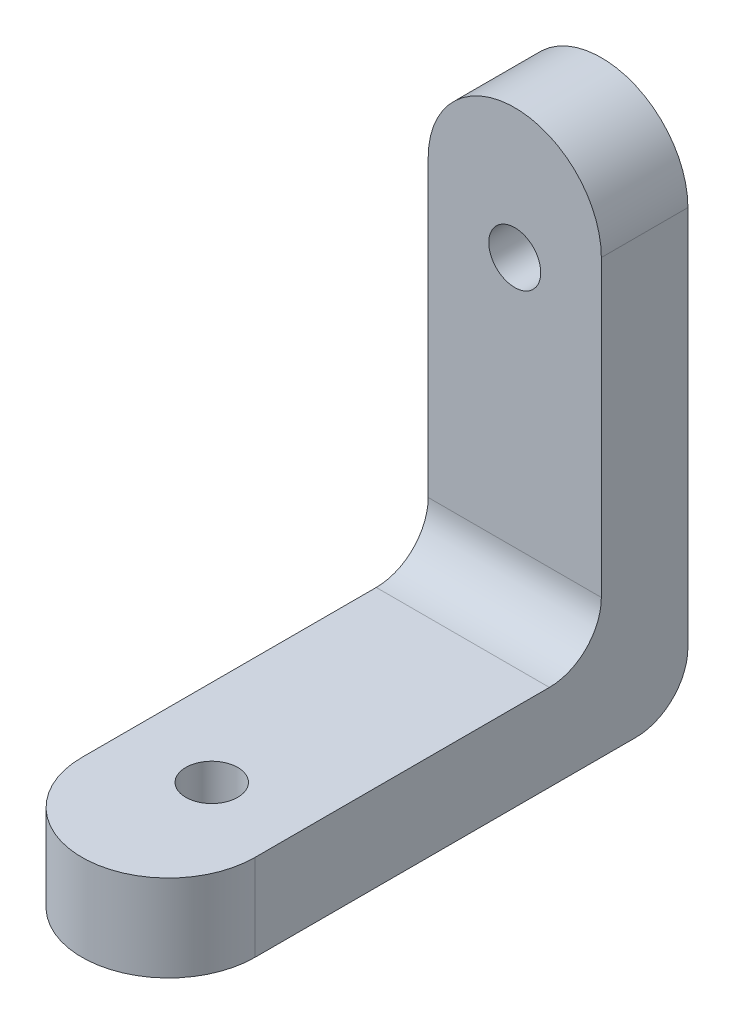
SolidWorks part; units mm, degrees
ref_plane "Plan de face" through (0, 0, 0) normal (0, 0, 1) x (1, 0, 0)
ref_plane "Plan de dessus" through (0, 0, 0) normal (0, 1, 0) x (1, 0, 0)
ref_plane "Plan de droite" through (0, 0, 0) normal (1, 0, 0) x (0, 0, -1)
sketch "Esquisse1" plane through (0, 0, 0) normal (0, 0, 1) x (1, 0, 0)
  line L1 (-5, 15) -> (5, 15)
  line L2 (-5, 15) -> (-5, -15)
  line L3 (-5, -15) -> (5, -15)
  line L4 (5, 15) -> (5, -15)
  line L5 (-5, 15) -> (5, -15) construction
  line L6 (-5, -15) -> (5, 15) construction
  point P0 (0, 0)
  dimension "D1" = 10
  dimension "D2" = 30
extrude "Boss.-Extru.1" add sketch "Esquisse1" along normal blind 5
sketch "Esquisse2" plane through (0, 0, 5) normal (0, 0, 1) x (1, 0, 0)
  line L0 (-5, -10) -> (5, -10)
  line L4 (5, -15) -> (5, 15)
  line L5 (5, 15) -> (-5, 15)
  line L6 (-5, 15) -> (-5, -15)
  line L7 (-5, -15) -> (5, -15)
  line L8 (5, -15) -> (5, -10)
  line L10 (-5, -10) -> (-5, -15)
  line L11 (-5, -15) -> (5, -15)
  dimension "D2" = 5
  dimension "D1" = 0
extrude "Boss.-Extru.2" add sketch "Esquisse2" along normal blind 25
sketch "Esquisse3" plane through (0, 0, 5) normal (0, 0, 1) x (1, 0, 0)
  line L0 (0, 15) -> (0, -10) construction
  line L1 (5, 15) -> (-5, 15) construction
  line L2 (5, -10) -> (-5, -10) construction
  circle A0 centre (0, 7.5) radius 1.5
  dimension "D2" = 3
  dimension "D1" = 7.5
extrude "Enlèv. mat.-Extru.1" cut sketch "Esquisse3" against normal blind 30
sketch "Esquisse4" plane through (0, -10, 0) normal (0, 1, 0) x (1, 0, 0)
  line L0 (0, -5) -> (0, -30) construction
  line L1 (5, -5) -> (-5, -5) construction
  line L2 (5, -30) -> (-5, -30) construction
  circle A0 centre (0, -22.5) radius 1.5
  dimension "D2" = 3
  dimension "D1" = 7.5
extrude "Enlèv. mat.-Extru.2" cut sketch "Esquisse4" against normal blind 30
fillet "Congé1" 2 edges at (-5, 15, 2.5) (5, 15, 2.5) type full round first side face at (-5, -3.3333, 11.6667) second side face at (5, -3.3333, 11.6667) middle face at (0, 15, 2.5)
fillet "Congé2" 2 edges at (-5, -12.5, 30) (5, -12.5, 30) type full round first side face at (-5, -5, 11.6667) second side face at (5, -5, 11.6667) middle face at (0, -12.5, 30)
fillet "Congé3" radius 3 1 edges at (0, -15, 0)
fillet "Congé4" radius 3 1 edges at (0, -10, 5) type face fillet first side face at (0, -10, 24) second side face at (1.5, 7.5, 5)
